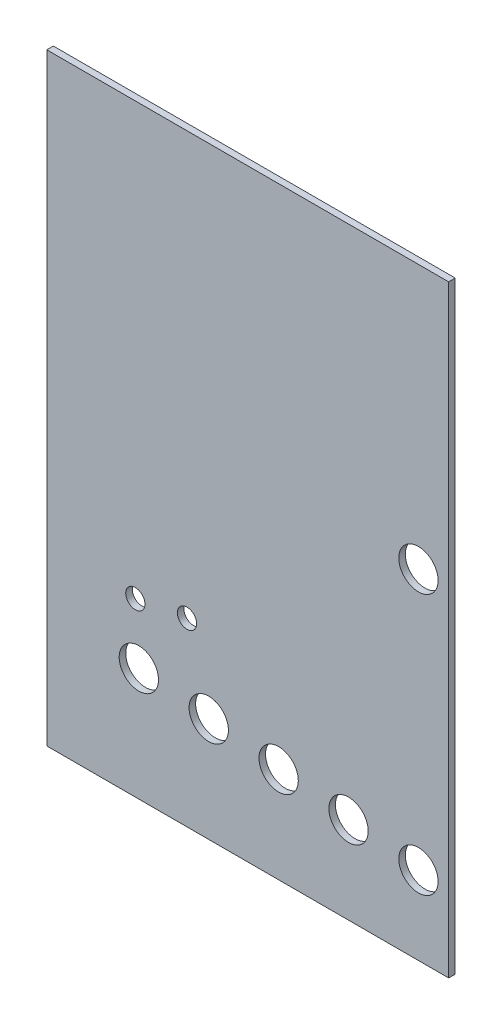
SolidWorks part; units mm, degrees
material "Polypropylene"
ref_plane "Front Plane" through (0, 0, 0) normal (0, 0, 1) x (1, 0, 0)
ref_plane "Top Plane" through (0, 0, 0) normal (0, 1, 0) x (1, 0, 0)
ref_plane "Right Plane" through (0, 0, 0) normal (1, 0, 0) x (0, 0, -1)
sketch "Sketch1" plane through (0, 0, 0) normal (0, 0, 1) x (1, 0, 0)
  line L0 (270.1144, -382.3444) -> (270.1144, -191.8444) construction
  line L1 (0, 0) -> (292.1, 0)
  line L2 (0, 0) -> (0, -438.15)
  line L3 (0, -438.15) -> (292.1, -438.15)
  line L4 (292.1, 0) -> (292.1, -438.15)
  circle A0 centre (64.3744, -313.2564) radius 7
  circle A1 centre (101.9257, -306.8134) radius 7
  circle A2 centre (101.9257, -306.8134) radius 7 construction
  circle A3 centre (64.3744, -313.2564) radius 7 construction
  circle A4 centre (270.1144, -191.8444) radius 14.2875
  dimension "D4" = 28.575
  dimension "D1" = 438.15
  dimension "D2" = 292.1
  dimension "D3" = 190.5
extrude "Boss-Extrude1" add sketch "Sketch1" along normal blind 4.7625
sketch "Sketch2" plane through (0, 0, 4.7625) normal (0, 0, 1) x (1, 0, 0)
  circle A1 centre (66.9144, -355.9045) radius 14.2875
  dimension "D1" = 28.575
extrude "Cut-Extrude1" cut sketch "Sketch2" against normal up to surface (4.7625 mm away) up to face at (146.05, -219.075, 0)
sketch "Sketch3" plane through (0, 0, 4.7625) normal (0, 0, 1) x (1, 0, 0)
  line L0 (66.9144, -355.9045) -> (292.1, -355.9045) construction
  line L1 (292.1, -438.15) -> (292.1, 0) construction
  line L2 (66.9144, -355.9045) -> (117.7144, -355.9045) construction
  line L3 (117.7144, -355.9045) -> (168.5144, -355.9045) construction
  line L4 (168.5144, -355.9045) -> (219.3144, -355.9045) construction
  line L5 (219.3144, -355.9045) -> (270.1144, -355.9045) construction
  line L6 (117.7144, -355.9045) -> (117.7144, -362.2545) construction
  line L7 (168.5144, -355.9045) -> (168.5144, -368.6045) construction
  line L8 (219.3144, -355.9045) -> (219.3144, -374.9545) construction
  line L9 (270.1144, -355.9045) -> (270.1144, -381.3045) construction
  line L10 (117.7144, -355.9045) -> (117.7144, -362.2545) construction
  circle A0 centre (117.7144, -362.2545) radius 14.2875
  circle A1 centre (168.5144, -368.6045) radius 14.2875
  circle A2 centre (219.3144, -374.9545) radius 14.2875
  circle A3 centre (270.1144, -381.3045) radius 14.2875
  dimension "D8" = 28.575
  dimension "D9" = 28.575
  dimension "D10" = 28.575
  dimension "D11" = 28.575
  dimension "D1" = 50.8
  dimension "D2" = 50.8
  dimension "D3" = 50.8
  dimension "D4" = 50.8
  dimension "D5" = 12.7
  dimension "D6" = 19.05
  dimension "D7" = 25.4
  dimension "D12" = 6.35
extrude "Cut-Extrude2" cut sketch "Sketch3" against normal up to surface (4.7625 mm away) contours A0 | A1 | A2 | A3 up to face at (81.2019, -355.9045, 0)
